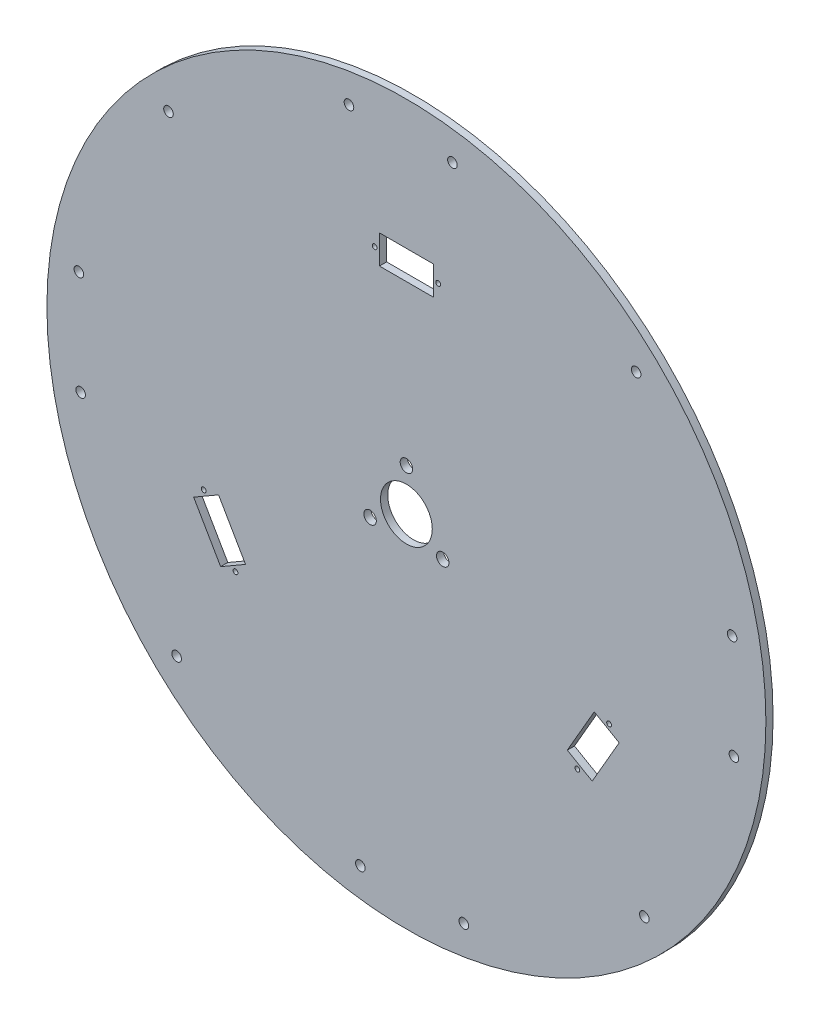
SolidWorks part; units mm, degrees
ref_plane "Alzado" through (0, 0, 0) normal (0, 0, 1) x (1, 0, 0)
ref_plane "Planta" through (0, 0, 0) normal (0, 1, 0) x (1, 0, 0)
ref_plane "Vista lateral" through (0, 0, 0) normal (1, 0, 0) x (0, 0, -1)
sketch "Croquis1" plane through (0, 0, 0) normal (0, 0, 1) x (1, 0, 0)
  line L0 (11.25, 96) -> (-11.25, 84) construction
  line L1 (-11.25, 96) -> (11.25, 96)
  line L2 (-11.25, 96) -> (-11.25, 84)
  line L3 (-11.25, 84) -> (11.25, 84)
  line L4 (11.25, 96) -> (11.25, 84)
  line L5 (-11.25, 96) -> (11.25, 84) construction
  line L6 (88.7634, -38.2572) -> (78.3711, -32.2572)
  line L7 (88.7634, -38.2572) -> (77.5134, -57.7428)
  line L8 (77.5134, -57.7428) -> (67.1211, -51.7428)
  line L9 (78.3711, -32.2572) -> (67.1211, -51.7428)
  line L10 (-77.5134, -57.7428) -> (-67.1211, -51.7428)
  line L11 (-77.5134, -57.7428) -> (-88.7634, -38.2572)
  line L12 (-88.7634, -38.2572) -> (-78.3711, -32.2572)
  line L13 (-67.1211, -51.7428) -> (-78.3711, -32.2572)
  line L14 (0, -0.7536) -> (0, 0) construction
  line L15 (0, 0) -> (0, 17.5) construction
  circle A0 centre (0, 0) radius 150
  circle A1 centre (0, 0) radius 10.8
  circle A2 centre (0, 0) radius 90 construction
  circle A3 centre (0, 90) radius 40 construction
  circle A4 centre (77.9423, -45) radius 40 construction
  circle A5 centre (-77.9423, -45) radius 40 construction
  circle A6 centre (0, 0) radius 17.5 construction
  circle A7 centre (0, 17.5) radius 2.6
  circle A9 centre (15.1554, -8.75) radius 2.6
  circle A10 centre (-15.1554, -8.75) radius 2.6
  point P11 (0, 90)
  point P18 (0, 0)
  point P28 (0, 0)
  point P39 (0, 0)
  dimension "D1" = 300
  dimension "D2" = 21.6
  dimension "D3" = 180
  dimension "D4" = 80
  dimension "D9" = 5.2
  dimension "D10" = 3
  dimension "D5" = 12
  dimension "D6" = 22.5
  dimension "D7" = 3
  dimension "D8" = 3
extrude "Saliente-Extruir1" add sketch "Croquis1" along normal blind 3
sketch "Croquis2" plane through (0, 0, 3) normal (0, 0, 1) x (1, 0, 0)
  circle A0 centre (0, 0) radius 130
  circle A1 centre (0, 0) radius 150 construction
  dimension "D1" = 20
sketch "Croquis3" plane through (0, 0, 3) normal (0, 0, 1) x (1, 0, 0)
  circle A0 centre (-99.2689, 95.8629) radius 2
  circle A2 centre (-23.9634, 135.9035) radius 2
  circle A3 centre (19.2059, 136.657) radius 2
  circle A4 centre (95.8629, 99.2689) radius 2
  circle A5 centre (135.9035, 23.9634) radius 2
  circle A6 centre (136.657, -19.2059) radius 2
  circle A7 centre (99.2689, -95.8629) radius 2
  circle A8 centre (23.9634, -135.9035) radius 2
  circle A9 centre (-19.2059, -136.657) radius 2
  circle A10 centre (-95.8629, -99.2689) radius 2
  circle A11 centre (-135.9035, -23.9634) radius 2
  circle A12 centre (-136.657, 19.2059) radius 2
  dimension "D1" = 4
extrude "Cortar-Extruir1" cut sketch "Croquis3" against normal through all
sketch "Croquis4" plane through (0, 0, 0) normal (0, 0, -1) x (-1, 0, 0)
  circle A0 centre (-13.25, 90) radius 1
  circle A1 centre (13.25, 90) radius 1
extrude "Cortar-Extruir2" cut sketch "Croquis4" against normal blind 10 contours A1 | A0
pattern_circular "MatrizC1" count 3 over 360 about axis through (0, 0, 0) along (0, 0, 1) of "Cortar-Extruir2"
